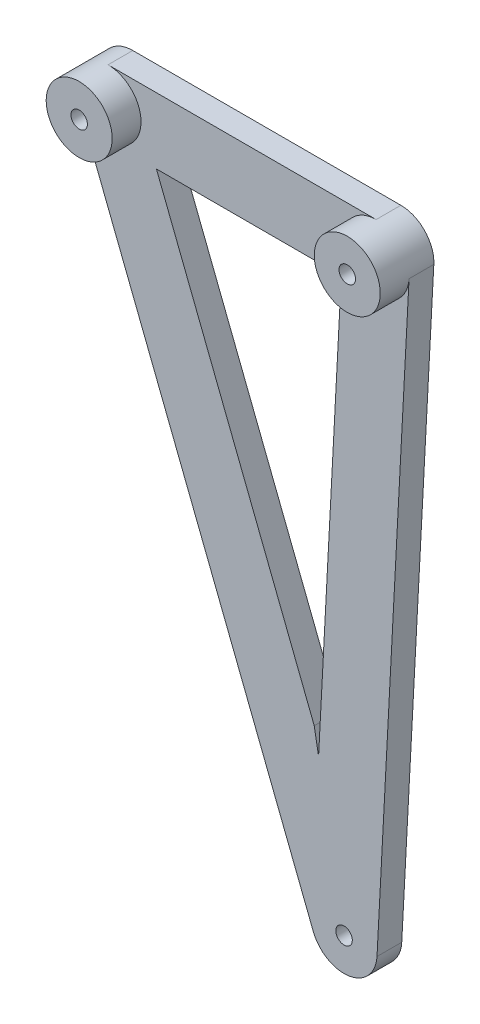
SolidWorks part; units mm, degrees
ref_plane "前视基准面" through (0, 0, 0) normal (0, 0, 1) x (1, 0, 0)
ref_plane "上视基准面" through (0, 0, 0) normal (0, 1, 0) x (1, 0, 0)
ref_plane "右视基准面" through (0, 0, 0) normal (1, 0, 0) x (0, 0, -1)
other "Configuration Table"
sketch "草图1" plane through (0, 0, 0) normal (0, 0, 1) x (1, 0, 0)
  line L3 (0, 0) -> (0, -30) construction
  line L5 (-16.25, -28.1458) -> (0, 0) construction
  line L6 (0, 0) -> (16.25, -28.1458) construction
  line L12 (-16.25, -24.1458) -> (16.25, -24.1458)
  line L13 (-16.25, -24.1458) -> (-16.25, -32.1458)
  line L14 (-16.25, -32.1458) -> (16.25, -32.1458)
  line L15 (16.25, -24.1458) -> (16.25, -32.1458)
  circle A4 centre (16.25, -28.1458) radius 1
  circle A5 centre (-16.25, -28.1458) radius 1
  circle A7 centre (-16.25, -28.1458) radius 1.75
  circle A8 centre (16.25, -28.1458) radius 1.75
  circle A9 centre (0, 0) radius 32.5 construction
  circle A10 centre (-16.25, -28.1458) radius 4
  circle A11 centre (16.25, -28.1458) radius 4
  point P2 (-15.0473, -24.9208)
  point P12 (0, 0)
  point P14 (0, 0)
  point P15 (0, 0)
  point P17 (16.25, -32.1458)
  dimension "D1" = 65
  dimension "D2" = 30
  dimension "D4" = 3.5
  dimension "D3" = 2
  dimension "D10" = 8
  dimension "D11" = 8
  dimension "D9" = 30
extrude "凸台-拉伸1" add sketch "草图1" along normal blind 3 contours L3 | L3 | A11 L12 A10 L14 | A11 | A10 | A4 | A5 region at (0, -28.1458, 0)
sketch "草图2" plane through (0, 0, 0) normal (0, 0, -1) x (-1, 0, 0)
  line L0 (-12.3617, -101.2524) -> (0, -32.1458) construction
  line L5 (16.25, -32.1458) -> (-16.25, -32.1458) construction
  line L6 (-16.356, -101.4648) -> (-20.2444, -28.3583)
  line L7 (-8.6368, -102.7102) -> (19.9749, -29.6036)
  line L8 (-8.3673, -101.0399) -> (-12.2556, -27.9334)
  line L9 (-16.0866, -99.7946) -> (12.5251, -26.688)
  circle A1 centre (-12.3617, -101.2524) radius 4
  circle A2 centre (-12.3617, -101.2524) radius 1
  arc A5 (-16.25, -24.1458) -> (-16.25, -32.1458) centre (-16.25, -28.1458) ccw construction
  arc A6 (16.25, -32.1458) -> (16.25, -24.1458) centre (16.25, -28.1458) ccw construction
  circle A7 centre (-16.25, -28.1458) radius 4
  circle A8 centre (16.25, -28.1458) radius 4
  arc M25 (-16.25, -24.1458) -> (-16.25, -32.1458) centre (-16.25, -28.1458) ccw
  line M26 (-16.25, -32.1458) -> (16.25, -32.1458)
  arc M27 (16.25, -32.1458) -> (16.25, -24.1458) centre (16.25, -28.1458) ccw
  circle M38 centre (16.25, -28.1458) radius 1
  circle M39 centre (-16.25, -28.1458) radius 1
  dimension "D1" = 2
extrude "凸台-拉伸2" add sketch "草图2" against normal up to surface (3 mm away) contours A1 L9 L8 L6 M26 M25 | L0 L8 A1 L7 L9 M27 M26 | L0 A1 L8 | A2 A1 | A1 L0 L8 L9 region at (9.4484, -98.6793, 0) region at (12.0077, -92.2829, 0) region at (9.7683, -93.5098, 0) region at (-3.104, -62.3582, 0) region at (14.676, -61.9052, 0) up to face at (0, -28.1458, 3)
extrude "凸台-拉伸4" add sketch "草图2<5>" against normal blind 3.5 from surface contours A7 M25 M39 | A8 M27 M38 region at (19.0705, -25.4714, 0) region at (-18.4411, -31.3563, 0) starting at face at (4.9156, -57.3302, 3)
sketch "草图2<5>" plane through (0, 0, 0) normal (0, 0, -1) x (-1, 0, 0) same geometry as "草图2"
extrude "切除-拉伸2" cut sketch "草图1<6>" along normal offset from surface (4.5 mm away) 2 contours A8 | A7 up to face at (20.25, -28.1458, 6.5)
sketch "草图1<6>" plane through (0, 0, 0) normal (0, 0, 1) x (1, 0, 0) same geometry as "草图1"
